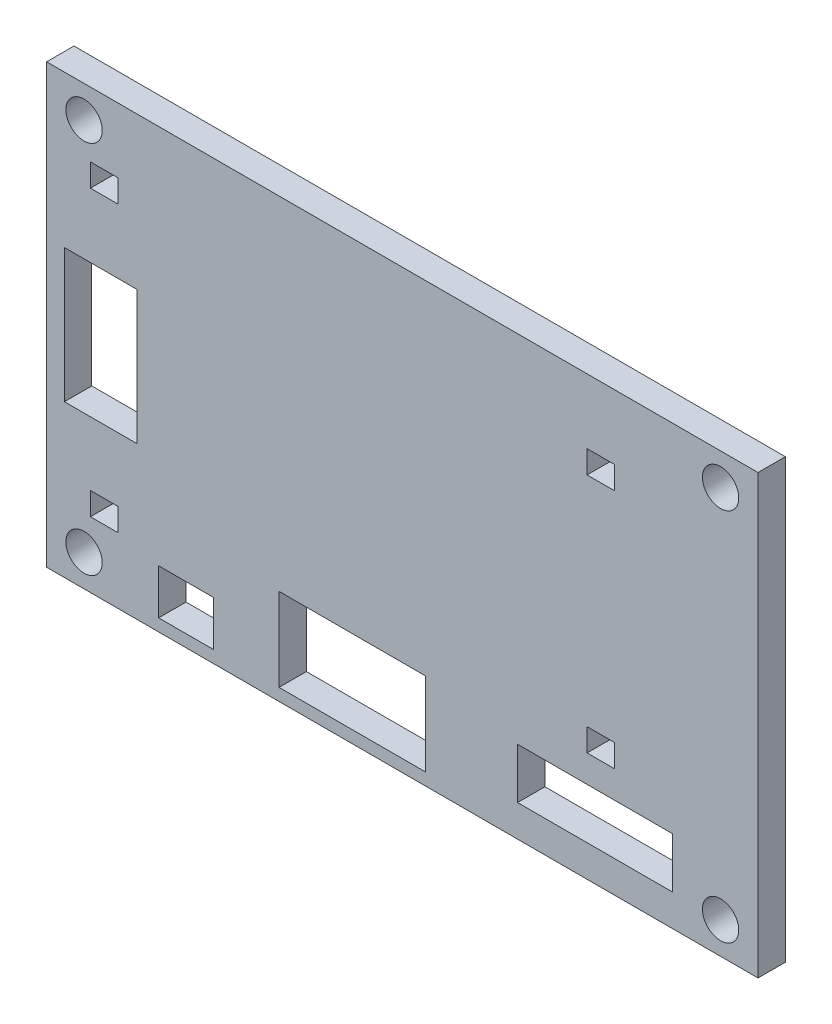
SolidWorks part; units mm, degrees
material "Beech"
ref_plane "Front Plane" through (0, 0, 0) normal (0, 0, 1) x (1, 0, 0)
ref_plane "Top Plane" through (0, 0, 0) normal (0, 1, 0) x (1, 0, 0)
ref_plane "Right Plane" through (0, 0, 0) normal (1, 0, 0) x (0, 0, -1)
sketch "Sketch1" plane through (0, 0, 0) normal (0, 0, 1) x (1, 0, 0)
  line L0 (-20.6375, 0) -> (20.6375, 0)
  line L44 (0, 14.605) -> (0, 24.13) construction
  line L46 (-20.6375, 0) -> (-20.6375, 25.4)
  line L47 (-20.6375, 25.4) -> (20.6375, 25.4)
  line L48 (20.6375, 0) -> (20.6375, 25.4)
  line L49 (-20.6375, 12.7) -> (20.6375, 12.7) construction
  circle A2 centre (-18.4658, 23.5585) radius 1.0541
  circle A3 centre (-18.4658, 1.8415) radius 1.0541
  circle A4 centre (18.4658, 1.8415) radius 1.0541
  circle A5 centre (18.4658, 23.5585) radius 1.0541
  point P0 (0, 0)
  point P56 (0, 12.7)
  point P60 (0, 25.4)
  dimension "D14" = 12.7
  dimension "D4" = 2.1082
  dimension "D3" = 25.4
  dimension "D12" = 41.275
  dimension "D5" = 2.1717
  dimension "D6" = 1.8415
extrude "Boss-Extrude1" add sketch "Sketch1" along normal blind 1.5875 contours L48 L47 L46 region at (0, 12.7, 0)
fillet "Fillet7" [suppressed] radius 15.24
sketch "Sketch2" plane through (0, 0, 1.5875) normal (0, 0, 1) x (1, 0, 0)
  line L4 (-20.6375, 0) -> (-20.6375, 25.4) construction
  line L5 (-20.6375, 25.4) -> (20.6375, 25.4) construction
  line L6 (-20.6375, 0) -> (20.6375, 0) construction
  line L7 (20.6375, 0) -> (20.6375, 25.4) construction
  line L8 (6.6858, 1.8395) -> (15.6858, 1.8395)
  line L9 (6.6858, 4.7695) -> (6.6858, 1.8395)
  line L10 (15.6858, 4.7695) -> (6.6858, 4.7695)
  line L11 (15.6858, 1.8395) -> (15.6858, 4.7695)
  line L12 (10.7188, 20.32) -> (10.7188, 21.6408) construction
  line L13 (10.7188, 21.6408) -> (12.3063, 21.6408) construction
  line L14 (12.3063, 21.6408) -> (12.3063, 20.32) construction
  line L15 (12.3063, 20.32) -> (10.7188, 20.32) construction
  line L16 (1.3552, 5.5335) -> (-7.1538, 5.5335)
  line L17 (1.3552, 0.7075) -> (1.3552, 5.5335)
  line L18 (-7.1538, 0.7075) -> (1.3552, 0.7075)
  line L19 (-7.1538, 5.5335) -> (-7.1538, 0.7075)
  line L20 (-18.0975, 20.32) -> (-18.0975, 21.6408) construction
  line L21 (-18.0975, 21.6408) -> (-16.51, 21.6408) construction
  line L22 (-16.51, 21.6408) -> (-16.51, 20.32) construction
  line L23 (-16.51, 20.32) -> (-18.0975, 20.32) construction
  line L24 (-10.9638, 3.3237) -> (-14.1388, 3.3237)
  line L25 (-10.9638, 0.7075) -> (-10.9638, 3.3237)
  line L26 (-14.1388, 0.7075) -> (-10.9638, 0.7075)
  line L27 (-14.1388, 3.3237) -> (-14.1388, 0.7075)
  line L28 (-18.0975, 3.81) -> (-18.0975, 5.1308) construction
  line L29 (-18.0975, 5.1308) -> (-16.51, 5.1308) construction
  line L30 (-16.51, 5.1308) -> (-16.51, 3.81) construction
  line L31 (-16.51, 3.81) -> (-18.0975, 3.81) construction
  line L32 (-19.6078, 8.834) -> (-15.3878, 8.834)
  line L33 (-19.6078, 16.584) -> (-19.6078, 8.834)
  line L34 (-15.3878, 16.584) -> (-19.6078, 16.584)
  line L35 (-15.3878, 8.834) -> (-15.3878, 16.584)
  line L48 (10.7188, 20.32) -> (10.7188, 21.6408)
  line L49 (10.7188, 21.6408) -> (12.3063, 21.6408)
  line L50 (12.3063, 21.6408) -> (12.3063, 20.32)
  line L51 (12.3063, 20.32) -> (10.7188, 20.32)
  line L52 (-18.0975, 20.32) -> (-18.0975, 21.6408)
  line L53 (-18.0975, 21.6408) -> (-16.51, 21.6408)
  line L54 (-16.51, 21.6408) -> (-16.51, 20.32)
  line L55 (-16.51, 20.32) -> (-18.0975, 20.32)
  line L56 (-18.0975, 3.81) -> (-18.0975, 5.1308)
  line L57 (-18.0975, 5.1308) -> (-16.51, 5.1308)
  line L58 (-16.51, 5.1308) -> (-16.51, 3.81)
  line L59 (-16.51, 3.81) -> (-18.0975, 3.81)
  line L64 (10.7188, 7.6708) -> (10.7188, 6.35)
  line L65 (12.3063, 7.6708) -> (10.7188, 7.6708)
  line L66 (12.3063, 6.35) -> (12.3063, 7.6708)
  line L67 (10.7188, 6.35) -> (12.3063, 6.35)
  line L68 (10.7188, 7.6708) -> (10.7188, 6.35)
  line L69 (12.3063, 7.6708) -> (10.7188, 7.6708)
  line L70 (12.3063, 6.35) -> (12.3063, 7.6708)
  line L71 (10.7188, 6.35) -> (12.3063, 6.35)
  dimension "D1" = 4.22
  dimension "D2" = 7.75
  dimension "D3" = 1.0297
  dimension "D4" = 8.816
  dimension "D5" = 3.175
  dimension "D6" = 2.6162
  dimension "D7" = 0.7075
  dimension "D8" = 6.4987
  dimension "D9" = 8.509
  dimension "D10" = 4.826
  dimension "D11" = 0.7075
  dimension "D12" = 19.2823
  dimension "D13" = 9
  dimension "D14" = 2.93
  dimension "D15" = 1.8395
  dimension "D16" = 4.9517
  dimension "D17" = 0
extrude "Cut-Extrude1" cut sketch "Sketch2" against normal up to surface (1.5875 mm away) up to face at (-17.4117, 1.8415, 0)
move or copy body "Body-Move/Copy1" [suppressed] bodies to move or copy 105
